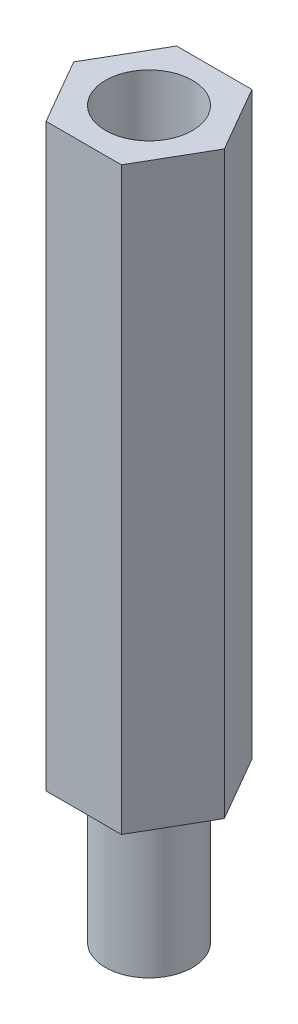
SolidWorks part; units mm, degrees
ref_plane "Front Plane" through (0, 0, 0) normal (0, 0, 1) x (1, 0, 0)
ref_plane "Top Plane" through (0, 0, 0) normal (0, 1, 0) x (1, 0, 0)
ref_plane "Right Plane" through (0, 0, 0) normal (1, 0, 0) x (0, 0, -1)
sketch "Sketch1" plane through (0, 0, 0) normal (0, 1, 0) x (1, 0, 0)
  line L1 (2.5981, 0) -> (1.299, 2.25)
  line L2 (1.299, 2.25) -> (-1.299, 2.25)
  line L3 (-1.299, 2.25) -> (-2.5981, 0)
  line L4 (-2.5981, 0) -> (-1.299, -2.25)
  line L5 (-1.299, -2.25) -> (1.299, -2.25)
  line L6 (1.299, -2.25) -> (2.5981, 0)
  circle A0 centre (0, 0) radius 2.25 construction
  dimension "D1" = 4.5
extrude "Boss-Extrude1" add sketch "Sketch1" along normal blind 20
sketch "Sketch2" plane through (0, 0, 0) normal (0, -1, 0) x (1, 0, 0)
  circle A0 centre (0, 0) radius 1.5
  dimension "D1" = 3
extrude "Boss-Extrude2" add sketch "Sketch2" along normal blind 5
extrude "Cut-Extrude1" cut sketch "Sketch2<2>" along normal blind 5 from surface starting at face at (0, 20, 0)
sketch "Sketch2<2>" plane through (0, 0, 0) normal (0, -1, 0) x (1, 0, 0) same geometry as "Sketch2"
